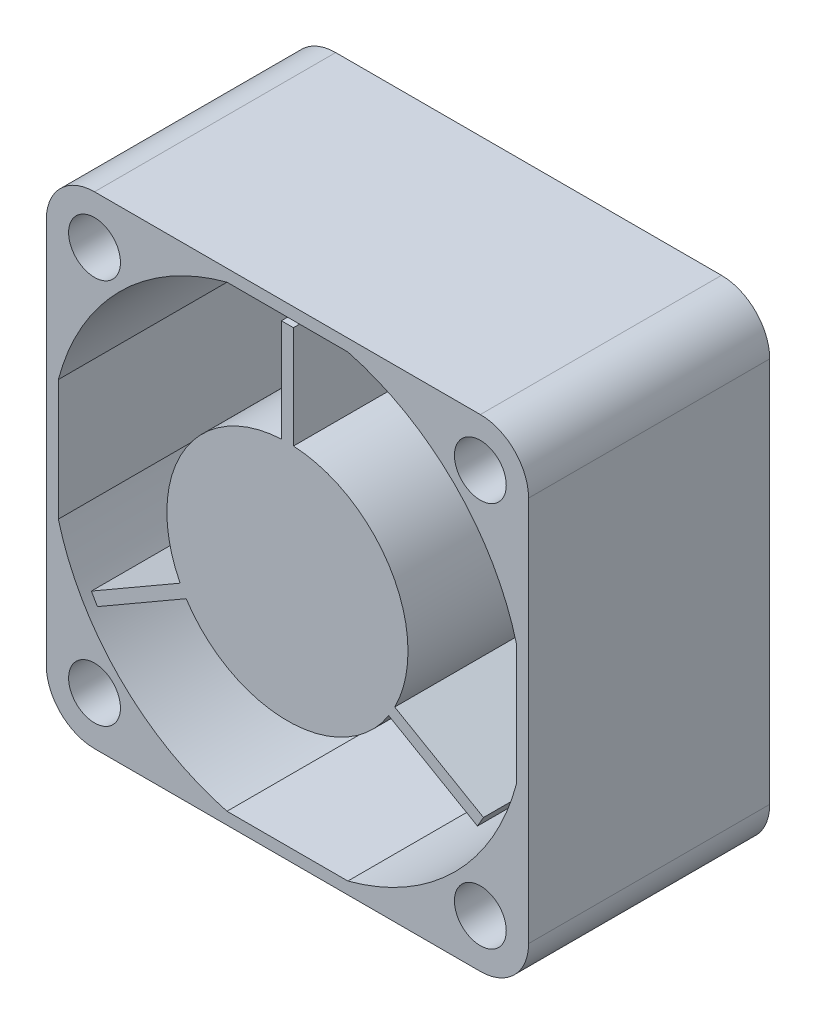
SolidWorks part; units mm, degrees
material "POM Acetal Copolymer"
ref_plane "Front Plane" through (0, 0, 0) normal (0, 0, 1) x (1, 0, 0)
ref_plane "Top Plane" through (0, 0, 0) normal (0, 1, 0) x (1, 0, 0)
ref_plane "Right Plane" through (0, 0, 0) normal (1, 0, 0) x (0, 0, -1)
sketch "Sketch1" plane through (0, 0, 0) normal (0, 0, 1) x (1, 0, 0)
  line L0 (0, 0) -> (0, 20) construction
  line L1 (-20, 20) -> (20, 20)
  line L2 (-20, 20) -> (-20, -20)
  line L3 (-20, -20) -> (20, -20)
  line L4 (20, 20) -> (20, -20)
  line L5 (0, 0) -> (20, 0) construction
  line L6 (-16, 16) -> (-16, -16) construction
  line L7 (-16, -16) -> (16, -16) construction
  line L8 (16, -16) -> (16, 16) construction
  line L9 (16, 16) -> (-16, 16) construction
  line L10 (-5.0122, 19) -> (5.0122, 19)
  line L11 (19, 5.0122) -> (19, -5.0122)
  line L12 (5.0122, -19) -> (-5.0122, -19)
  line L13 (-19, -5.0122) -> (-19, 5.0122)
  arc A0 (-19, -5.0122) -> (-5.0122, -19) centre (0, 0) ccw
  circle A1 centre (-16, 16) radius 2.15
  circle A2 centre (16, 16) radius 2.15
  circle A3 centre (16, -16) radius 2.15
  circle A4 centre (-16, -16) radius 2.15
  arc A5 (-5.0122, 19) -> (-19, 5.0122) centre (0, 0) ccw
  arc A6 (19, 5.0122) -> (5.0122, 19) centre (0, 0) ccw
  arc A7 (5.0122, -19) -> (19, -5.0122) centre (0, 0) ccw
  dimension "D2" = 39.3
  dimension "D3" = 4.3
  dimension "D1" = 40
  dimension "D4" = 32
  dimension "D5" = 1
extrude "Boss-Extrude1" add sketch "Sketch1" along normal blind 10 and the other way blind 10
fillet "Fillet1" radius 4 4 edges at (-20, -20, 0) (20, -20, 0) (20, 20, 0) (-20, 20, 0)
sketch "Sketch2" plane through (0, 0, 10) normal (0, 0, 1) x (1, 0, 0)
  line L0 (-8.8994, -4.5607) -> (-16.2606, -8.8107)
  line L1 (-0.5, 18.4875) -> (0.5, 18.4875)
  line L2 (-0.5, 18.4875) -> (-0.5, 9.9875)
  line L3 (0, 0) -> (-16.0106, -9.2437) construction
  line L4 (0.5, 18.4875) -> (0.5, 9.9875)
  line L5 (-16.2606, -8.8107) -> (-15.7606, -9.6768)
  line L6 (-15.7606, -9.6768) -> (-8.3994, -5.4268)
  line L7 (8.3994, -5.4268) -> (15.7606, -9.6768)
  line L8 (15.7606, -9.6768) -> (16.2606, -8.8107)
  line L9 (16.2606, -8.8107) -> (8.8994, -4.5607)
  line L10 (0, 0) -> (0, 18.4875) construction
  line L11 (0, 0) -> (16.0106, -9.2437) construction
  arc A0 (-0.5, 9.9875) -> (-8.8994, -4.5607) centre (0, 0) ccw
  arc A1 (-8.3994, -5.4268) -> (8.3994, -5.4268) centre (0, 0) ccw
  arc A2 (8.8994, -4.5607) -> (0.5, 9.9875) centre (0, 0) ccw
  dimension "D1" = 20
  dimension "D2" = 8.5
  dimension "D3" = 1
  dimension "D4" = 120
  dimension "D5" = 120
extrude "Boss-Extrude2" add sketch "Sketch2" against normal up to surface (20 mm away) separate body up to face at (0, 0, -10)
